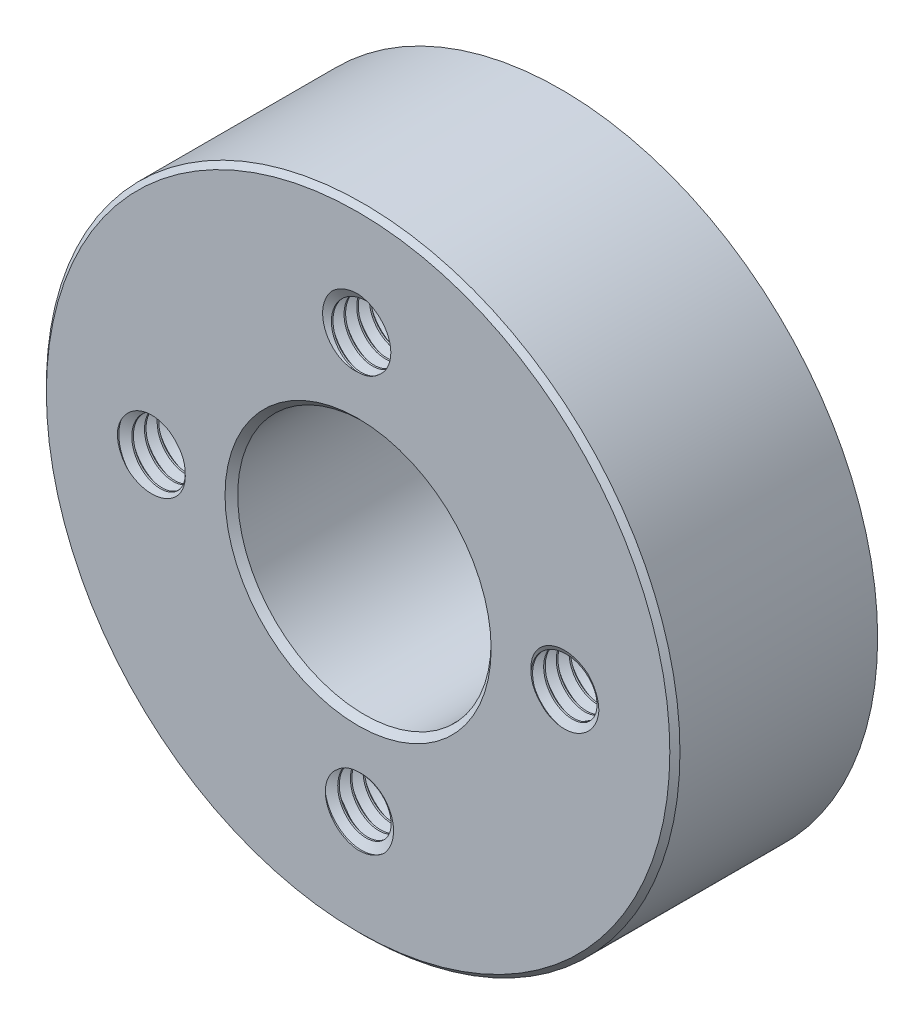
SolidWorks part; units mm, degrees
note: '?' marks a value the reader was unsure of.
ref_plane "Front Plane" through (0, 0, 0) normal (0, 0, 1) x (1, 0, 0)
ref_plane "Top Plane" through (0, 0, 0) normal (0, 1, 0) x (1, 0, 0)
ref_plane "Right Plane" through (0, 0, 0) normal (1, 0, 0) x (0, 0, -1)
sketch "Sketch2" plane through (0, 0, 0) normal (0, 0, 1) x (1, 0, 0)
  line L0 (0, 17.75) -> (0, 9.5) construction
  line L1 (0, 13.4) -> (0, 12.5) construction
  circle A0 centre (0, 0) radius 21 construction
  circle A1 centre (0, 0) radius 8 construction
  circle A2 centre (0, 0) radius 5
  circle A3 centre (0, 0) radius 26
  circle A4 centre (0, 21) radius 3.25
  circle A5 centre (0, 8) radius 1.5
  circle A6 centre (0, 21) radius 1.7
  circle A7 centre (0, 0) radius 12.95 construction
  point P14 (0, 12.95)
  dimension "BC1" = 16
  dimension "BC2" = 42
  dimension "ID" = 10
  dimension "OD" = 52
  dimension "Mounting Hole Counterbore" = 6.5
  dimension "Mounting Hole Thread Size" = 3
  dimension "Mounting Hole Diameter" = 3.4
  dimension "D1" = 8.25
  dimension "D3" = 0.9
  dimension "D2" = 4.95
sketch "Sketch3" plane through (0, 0, 0) normal (1, 0, 0) x (0, 0, -1)
  line L0 (-4, 0) -> (4, 0) construction
  line L1 (4, 26) -> (-4, 26) construction
  line L2 (-4, 26) -> (-4, 0) construction
  line L3 (-4, 24.25) -> (-0.7, 24.25)
  line L4 (-0.7, 24.25) -> (-0.7, 17.75)
  line L5 (-0.7, 17.75) -> (-4, 17.75)
  line L7 (-0.7, 24.25) -> (0, 24.25) construction
  line L10 (-0.7, 17.75) -> (0, 17.75) construction
  line L11 (-4, 0) -> (-4, -26) construction
  line L12 (-4, -26) -> (4, -26) construction
  point P7 (0, 26)
  dimension "Counterbore Depth" = 3.3
  dimension "Width" = 8
ref_axis "Axis1" through (0, 0, 4) along (0, 0, -1)
sketch "Sketch4" plane through (0, 0, 0) normal (0, 0, 1) x (1, 0, 0)
  circle A0 centre (0, 8) radius 1.5 construction
  circle A1 centre (0, 8) radius 1.5
extrude "Boss-Extrude1" add sketch "Sketch4" along normal up to vertex (4 mm away) and the other way up to vertex (4 mm away) up to point (0, 0, 4) other way up to point (0, 0, -4)
sketch "Sketch5" plane through (0, 0, 4) normal (0, 0, 1) x (1, 0, 0)
  circle A0 centre (0, 8) radius 1.5 construction
  circle A1 centre (0, 8) radius 1.5
sketch "Sketch7" plane through (0, 0, 4) normal (0, 0, 1) x (1, 0, 0)
  circle A0 centre (0, 8) radius 1.5 construction
  circle A1 centre (0, 8) radius 1.5
extrude "Boss-Extrude2" add sketch "Sketch7" against normal through all draft 45
sketch "Sketch8" plane through (0, 0, -4) normal (0, 0, -1) x (-1, 0, 0)
  circle A1 centre (0, 8) radius 1.5
  circle A2 centre (0, 8) radius 1.5
  dimension "D1" = 0
extrude "Boss-Extrude3" add sketch "Sketch8" against normal through all draft 45
pattern_circular "CirPattern1" count 4 over 360 about axis through (0, 0, 0) along (0, 0, 1) of bodies 104
sketch "Sketch9" plane through (0, 0, 0) normal (0, 0, 1) x (1, 0, 0)
  circle A0 centre (0, 0) radius 26 construction
  circle A1 centre (0, 0) radius 5 construction
  circle A2 centre (0, 0) radius 26
  circle A3 centre (0, 0) radius 5
extrude "Boss-Extrude4" add sketch "Sketch9" against normal up to vertex (4 mm away) and the other way up to vertex (4 mm away) separate body up to point (0, 0, -4) other way up to point (0, 0, 4)
combine bodies "Combine1" operation type subtract main body 112 bodies to subtract 107 105 106 104
sketch "Sketch10" plane through (0, 0, 4) normal (0, 0, 1) x (1, 0, 0)
  circle A0 centre (0, 21) radius 3.25 construction
  circle A1 centre (0, 21) radius 3.25
extrude "Cut-Extrude1" cut sketch "Sketch10" against normal up to vertex (3.3 mm away) up to point (0, 17.75, 0.7)
sketch "Sketch11" plane through (0, 0, 4) normal (0, 0, 1) x (1, 0, 0)
  circle A0 centre (0, 21) radius 1.7 construction
  circle A1 centre (0, 21) radius 1.7
extrude "Cut-Extrude2" cut sketch "Sketch11" against normal through all
chamfer "Chamfer2" distance 0.25 angle 45 1 edges at (3.25, 21, 4)
chamfer "Chamfer1" distance 0.25 angle 45 4 edges at (5, 0, 4) (5, 0, -4) (26, 0, 4) (26, 0, -4)
pattern_circular "CirPattern2" count 6 over 360 about axis through (0, 0, 0) along (0, 0, 1) of "Cut-Extrude2", "Cut-Extrude1", "Chamfer2"
sketch "Sketch12" plane through (0, 0, 0) normal (1, 0, 0) x (0, 0, -1)
  line L1 (-4, 13.4) -> (-3, 13.4)
  line L2 (-4, 13.4) -> (-4, 12.5)
  line L3 (-4, 12.5) -> (-3, 12.5)
  line L4 (-3, 13.4) -> (-3, 12.5)
  line L5 (3, 13.4) -> (4, 13.4)
  line L6 (3, 13.4) -> (3, 12.5)
  line L7 (3, 12.5) -> (4, 12.5)
  line L8 (4, 13.4) -> (4, 12.5)
  line L9 (-0.8, 26) -> (0.8, 26)
  line L10 (-0.8, 26) -> (-0.8, 25.7)
  line L11 (-0.8, 25.7) -> (0.8, 25.7)
  line L12 (0.8, 26) -> (0.8, 25.7)
  line L13 (-4, 25.75) -> (-4, -25.75) construction
  line L14 (4, -25.75) -> (4, 25.75) construction
  line L15 (3.75, 26) -> (-3.75, 26) construction
  line L16 (0, 26) -> (0, -26) construction
  point P20 (0, 25.7)
  dimension "D1" = 1.6
  dimension "D2" = 0.3
  dimension "Seal Type" = 1
revolve "Cut-Revolve1" cut sketch "Sketch12" angle 360 about axis through (0, 0, 4) along (0, 0, -1)
ref_plane "Plane1" through (0, 0, 0) normal (0.866, -0.5, 0) x (0, 0, -1)
sketch "Sketch13" plane through (0, 0, 0) normal (0.866, -0.5, 0) x (0, 0, -1)
  line L0 (0, 30.9772) -> (0, 12.95) construction
  line L3 (0, 26) -> (0, -26) construction
  line L4 (0, 12.95) -> (-0.44, 12.95)
  line L5 (0, 12.95) -> (0, 26)
  line L6 (0, 26) -> (-0.44, 26)
  line L7 (-0.44, 12.95) -> (-0.44, 26)
  dimension "D1" = 0.88
revolve "Cut-Revolve2" cut sketch "Sketch13" angle 360 about L0
pattern_circular "CirPattern3" count 2 over 360 about axis through (0, 0, 4) along (0, 0, -1) of "Cut-Revolve2"
chamfer "Chamfer3" distance 0.2 angle 45 2 edges at (12.5, 0, 4) (13.4, 0, 4)
sketch "Note Point" plane through (0, 0, 0) normal (0, 0, 1) x (1, 0, 0)
  line L0 (0, 8) -> (0, 6.5) construction
  line L1 (0, 8) -> (0, 9.5) construction
  circle A1 centre (0, 8) radius 1.5 construction
  point P0 (0, 6.5)
  point P1 (0, 8)
  point P7 (0, 9.5)
curve "Helix/Spiral1" pitch 0.5 height 8.5 turns 17 parameters "Pitch"=0.5
ref_plane "Contact Plane1 " through (0, 0, -4) normal (0, 0, -1) x (-1, 0, 0)
ref_axis "Center Axis 1" through (0, 0, -8.6398) along (0, 0, 1)?
sketch "Sketch6" plane through (0, 0, 0) normal (1, 0, 0) x (0, 0, -1)
  line L0 (-4.4375, 9.5) -> (-4, 9.5)
  line L1 (-4.4375, 9.5) -> (-4.25, 9.1752)
  line L2 (-4.25, 9.1752) -> (-4.1875, 9.1752)
  line L3 (-4.1875, 9.1752) -> (-4, 9.5)
  line L4 (-4.2187, 9.1752) -> (-4.2187, 9.5) construction
  line L5 (-4.3437, 9.3376) -> (-4.0937, 9.3376) construction
  dimension "D1" = 60
  dimension "D2" = 0.0625
  dimension "D3" = 0.25
sweep "Sweep1" add profiles "Sketch6" path "Helix/Spiral1"
sketch "Sketch14" plane through (0, 0, 4) normal (0, 0, 1) x (1, 0, 0)
  circle A0 centre (0, 8) radius 1.5 construction
  circle A1 centre (0, 8) radius 1.5
extrude "Cut-Extrude3" cut sketch "Sketch14" along normal blind 5 draft 60 draft outward yes
sketch "Sketch15" plane through (0, 0, -4) normal (0, 0, -1) x (-1, 0, 0)
  circle A0 centre (0, 8) radius 1.5 construction
  circle A1 centre (0, 8) radius 1.5
extrude "Cut-Extrude4" cut sketch "Sketch15" along normal blind 5 draft 60 draft outward yes
pattern_circular "CirPattern5" count 4 over 360 about axis through (0, 0, 4) along (0, 0, 1) of "Cut-Extrude4", "Sweep1", "Cut-Extrude3"
sketch "Sketch16" plane through (0, 0, 4) normal (0, 0, 1) x (1, 0, 0)
  circle A0 centre (0, 0) radius 12.5
  circle A1 centre (0, 0) radius 43.36
extrude "Cut-Extrude5" cut sketch "Sketch16" against normal blind 10
equation "\"D3@Helix/Spiral1\"=\"Width@Sketch3\"+\"Pitch@Helix/Spiral1\""
equation "\"D2@Sketch6\"=\"Pitch@Helix/Spiral1\"*.125"
equation "\"D3@Sketch6\"=\"Pitch@Helix/Spiral1\"*.50"
equation "\"D1@Sketch12\"=\"Width@Sketch3\"/5"
equation "\"D1@Plane1\"=(360/\"outer ring hole number@CirPattern2\")/2"
equation "\"D1@Sketch13\"=\"D1@Sketch12\"*.55"
equation "\"D1@CirPattern5\"=\"Mounting Hole Number@CirPattern1\""
equation "\"D2@Sketch2\"=\"D1@Sketch2\"*.6"
